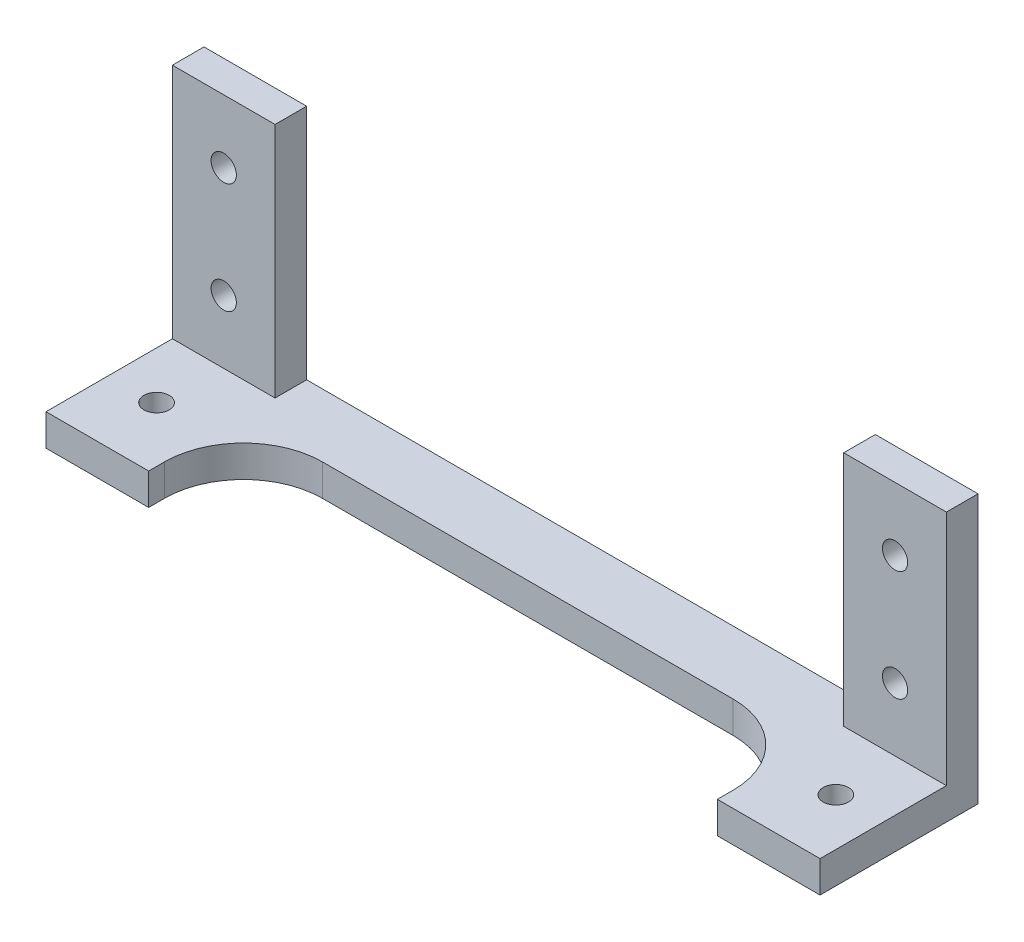
SolidWorks part; units mm, degrees
ref_plane "Front Plane" through (0, 0, 0) normal (0, 0, 1) x (1, 0, 0)
ref_plane "Top Plane" through (0, 0, 0) normal (0, 1, 0) x (1, 0, 0)
ref_plane "Right Plane" through (0, 0, 0) normal (1, 0, 0) x (0, 0, -1)
sketch "Sketch1" plane through (0, 0, 0) normal (0, 0, 1) x (1, 0, 0)
  line L0 (42.5, 17) -> (49, 17)
  line L1 (0, 0) -> (49, 0)
  line L2 (0, 0) -> (0, 17)
  line L3 (0, 17) -> (6.5, 17)
  line L4 (49, 0) -> (49, 17)
  line L5 (6.5, 17) -> (6.5, 2)
  line L6 (6.5, 2) -> (42.5, 2)
  line L7 (42.5, 2) -> (42.5, 17)
extrude "Boss-Extrude1" add sketch "Sketch1" along normal blind 2
sketch "Sketch2" plane through (0, 0, 2) normal (0, 0, 1) x (1, 0, 0)
  line L0 (49, 0) -> (49, 17) construction
  line L1 (0, 0) -> (49, 0)
  line L2 (0, 0) -> (0, 2)
  line L3 (0, 2) -> (49, 2)
  line L4 (49, 0) -> (49, 2)
extrude "Boss-Extrude2" add sketch "Sketch2" along normal blind 8
sketch "Sketch3" plane through (0, 0, 2) normal (0, 0, 1) x (1, 0, 0)
  line L0 (3.25, 17) -> (3.25, 2) construction
  line L1 (6.5, 17) -> (0, 17) construction
  line L2 (6.5, 2) -> (0, 2) construction
  line L3 (45.75, 17) -> (45.75, 2) construction
  circle A0 centre (3.25, 13) radius 0.8
  circle A1 centre (3.25, 6) radius 0.8
  circle A2 centre (45.75, 13) radius 0.8
  circle A3 centre (45.75, 6) radius 0.8
  dimension "D1" = 4
  dimension "D2" = 4
  dimension "D3" = 4
  dimension "D4" = 4
extrude "Cut-Extrude1" cut sketch "Sketch3" against normal blind 2
sketch "Sketch4" plane through (0, 2, 0) normal (0, 1, 0) x (1, 0, 0)
  line L0 (0, -6) -> (49, -6) construction
  line L1 (0, -10) -> (0, -2) construction
  line L2 (49, -10) -> (49, -2) construction
  circle A0 centre (3, -6) radius 0.8
  circle A1 centre (46, -6) radius 0.8
  dimension "D1" = 3
  dimension "D2" = 3
extrude "Cut-Extrude2" cut sketch "Sketch4" against normal blind 2
sketch "Sketch5" plane through (0, 2, 0) normal (0, 1, 0) x (1, 0, 0)
  line L0 (6.5, -10) -> (6.5, -9)
  line L1 (49, -10) -> (0, -10) construction
  line L2 (11.5, -4) -> (37.5, -4)
  line L3 (42.5, -9) -> (42.5, -10)
  line L4 (6.5, -10) -> (42.5, -10)
  arc A0 (37.5, -4) -> (42.5, -9) centre (37.5, -9) cw
  arc A1 (6.5, -9) -> (11.5, -4) centre (11.5, -9) cw
  dimension "D1" = 5
extrude "Cut-Extrude3" cut sketch "Sketch5" against normal blind 2
ref_axis "Axis1" through (3, -5.0239, 6) along (0, 1, 0)
ref_axis "Axis2" through (46, -6.9079, 6) along (0, 1, 0)
